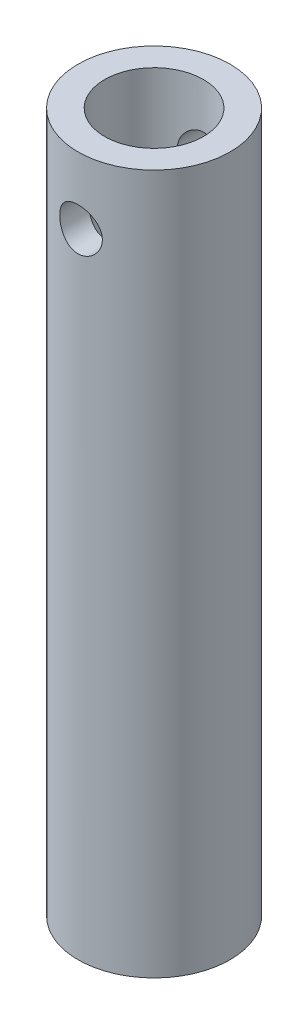
SolidWorks part; units mm, degrees
ref_plane "Front Plane" through (0, 0, 0) normal (0, 0, 1) x (1, 0, 0)
ref_plane "Top Plane" through (0, 0, 0) normal (0, 1, 0) x (1, 0, 0)
ref_plane "Right Plane" through (0, 0, 0) normal (1, 0, 0) x (0, 0, -1)
sketch "Sketch1" plane through (0, 0, 0) normal (0, 0, 1) x (1, 0, 0)
  line L0 (2.15, 0) -> (5, 0)
  line L1 (5, 0) -> (5, 46)
  line L2 (5, 46) -> (3.25, 46)
  line L4 (2.15, 0) -> (2.15, 12)
  line L5 (2.15, 12) -> (3.25, 12)
  line L6 (3.25, 12) -> (3.25, 46)
  line L7 (0, 0) -> (0, 46) construction
  point P2 (0, 0)
  point P7 (0, 0)
  dimension "D1" = 2.15
  dimension "D2" = 3.25
  dimension "D3" = 5
  dimension "D4" = 12
  dimension "D5" = 34
revolve "Revolve1" add sketch "Sketch1" angle 360 about L7
sketch "Sketch2" plane through (0, 0, 0) normal (0, 0, 1) x (1, 0, 0)
  line L0 (0, 46) -> (0, 43) construction
  line L1 (3.25, 46) -> (-3.25, 46) construction
  circle A0 centre (0, 41.6) radius 1.4
  point P5 (0, 40.2764)
  dimension "D1" = 2.8
  dimension "D2" = 3
extrude "Cut-Extrude1" cut sketch "Sketch2" against normal blind 10 and the other way blind 10
